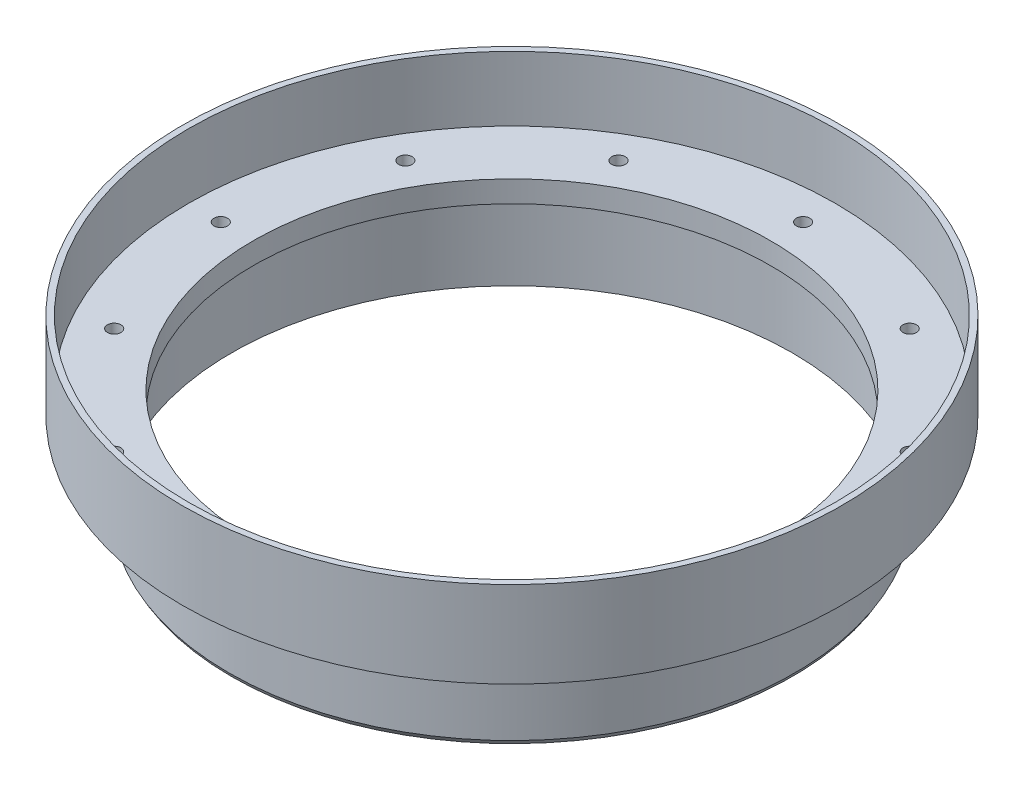
SolidWorks part; units mm, degrees
material "6061-T6 (SS)"
ref_plane "Front Plane" through (0, 0, 0) normal (0, 0, 1) x (1, 0, 0)
ref_plane "Top Plane" through (0, 0, 0) normal (0, 1, 0) x (1, 0, 0)
ref_plane "Right Plane" through (0, 0, 0) normal (1, 0, 0) x (0, 0, -1)
ref_axis "Axis1" through (0, 55, 0) along (0, -1, 0)
sketch "Cross Section" plane through (0, 0, 0) normal (0, 0, 1) x (1, 0, 0)
  line L0 (-38.1, 0) -> (-38.1, -3.175)
  line L1 (-38.1, -3.175) -> (-41.275, -3.175)
  line L2 (-41.275, -3.175) -> (-41.275, -15.875)
  line L3 (-41.275, -15.875) -> (-41.656, -15.2151)
  line L4 (0, -15.875) -> (-38.1, -15.875) construction
  line L5 (-41.656, -15.2151) -> (-41.656, -3.175)
  line L6 (-41.656, -3.175) -> (-48.514, -3.175)
  line L7 (-48.514, -3.175) -> (-48.514, 9.525)
  line L8 (-48.514, 9.525) -> (-47.625, 9.525)
  line L9 (-47.625, 9.525) -> (-47.625, 0)
  line L10 (-47.625, 0) -> (-38.1, 0)
  line L11 (-38.1, 0) -> (0, 0) construction
  line L12 (0, 55) -> (0, -55) construction
  line L14 (-47.625, 1.5875) -> (-47.625, 3.175) construction
  dimension "D1" = 3.175
  dimension "D3" = 0.381
  dimension "D4" = 30
  dimension "D5" = 6.858
  dimension "D6" = 12.7
  dimension "D9" = 3.175
  dimension "D8" = 38.1
revolve "Main" add sketch "Cross Section" angle 360 about axis through (0, 55, 0) along (0, -1, 0)
sketch "Hole Location" plane through (0, 0, 0) normal (0, 1, 0) x (1, 0, 0)
  line L0 (0, 0) -> (-42.8625, 0) construction
  circle A0 centre (0, 0) radius 42.8625 construction
  dimension "D1" = 85.725
hole_wizard "#3-48 Tapped Hole1" positions "Sketch5" profile "Sketch7" tap size "#3-48" standard "ANSI Inch"
sketch "Sketch5" plane through (0, 0, 0) normal (0, 1, 0) x (1, 0, 0)
  point P0 (-42.8625, 0)
sketch "Sketch7" plane through (-42.8625, 0, 0) normal (1, 0, 0) x (0, 0, 1)
  line L0 (0, 0) -> (0, 3.901)
  line L1 (0, 3.901) -> (0.9969, 3.302)
  line L2 (0.9969, 3.302) -> (0.9969, 0)
  line L5 (0.9969, 0) -> (0, 0)
  line L10 (0, 3.901) -> (-0.997, 3.302) construction
  line L11 (0, -6.35) -> (0, 107.95) construction
  dimension "Tap Drill Dia." = 1.9939
  dimension "Tap Drill Depth" = 3.302
  dimension "Drill Angle" = 118
cosmetic thread "Hole Thread1" parameters "D1"=3.175, "D2"=2.5146
pattern_circular "Screw Holes" count 12 over 360 about axis through (0, 55, 0) along (0, -1, 0) of "#3-48 Tapped Hole1"
equation "\"D8@Cross Section\"=\"TANK DIAMETER@Cryo Tank.Assembly\"/2"
equation "\"D1@Hole Location\"=\"TANK DIAMETER@Cryo Tank.Assembly\"+\"GASKET SEAT THICKNESS@Cryo Tank.Assembly\""
equation "\"D1@Cross Section\"=\"LINER THICKNESS@Cryo Tank.Assembly\""
equation "\"D3@Cross Section\"=\"ALUMINUM LAP THICKNESS@Cryo Tank.Assembly\""
equation "\"D5@Cross Section\"=2*\"CF THICKNESS@Cryo Tank.Assembly\"+\"NOMEX THICKNESS@Cryo Tank.Assembly\""
